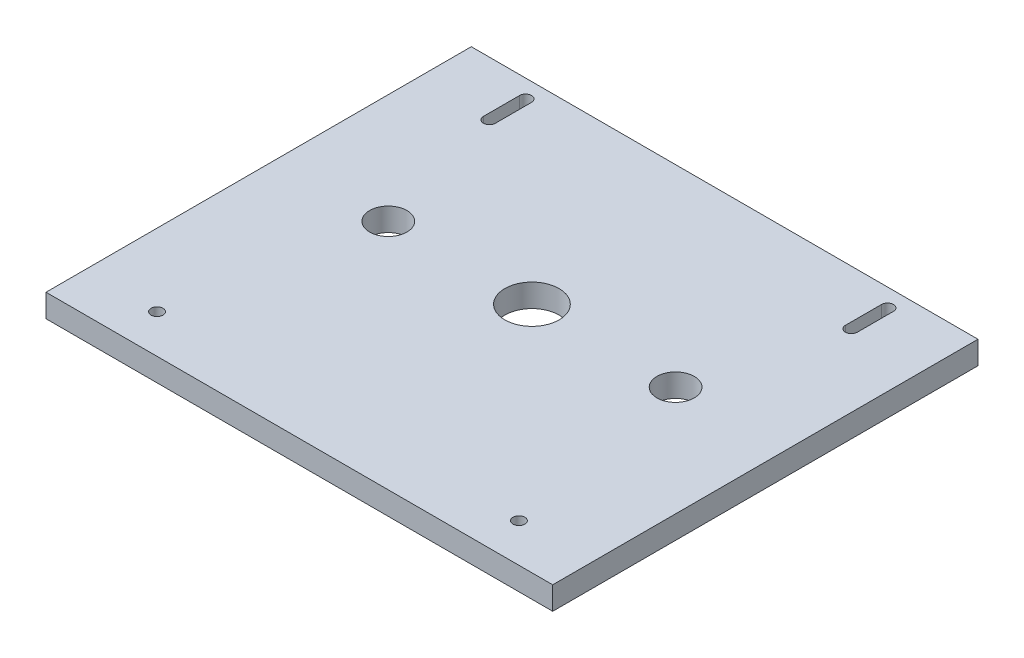
SolidWorks part; units mm, degrees
ref_plane "Front Plane" through (0, 0, 0) normal (0, 0, 1) x (1, 0, 0)
ref_plane "Top Plane" through (0, 0, 0) normal (0, 1, 0) x (1, 0, 0)
ref_plane "Right Plane" through (0, 0, 0) normal (1, 0, 0) x (0, 0, -1)
sketch "Sketch1" plane through (0, 0, 0) normal (0, 1, 0) x (1, 0, 0)
  line L1 (0, 0) -> (140, 0)
  line L2 (0, 0) -> (0, 117.505)
  line L3 (0, 117.505) -> (140, 117.505)
  line L4 (140, 0) -> (140, 117.505)
  dimension "D1" = 117.505
  dimension "D2" = 140
extrude "Boss-Extrude1" add sketch "Sketch1" along normal blind 6.35
sketch "Sketch2" plane through (0, 6.35, 0) normal (0, 1, 0) x (1, 0, 0)
  line L1 (0, 117.505) -> (0, 0) construction
  line L2 (140, 0) -> (140, 117.505) construction
  line L3 (70, 117.505) -> (70, 0) construction
  line L4 (140, 117.505) -> (0, 117.505) construction
  line L5 (0, 0) -> (140, 0) construction
  line L6 (0, 10.675) -> (140, 10.675) construction
  line L7 (0, 107.505) -> (140, 107.505) construction
  line L8 (120, 102.505) -> (120, 112.505) construction
  line L11 (20, 102.505) -> (20, 112.505) construction
  line L12 (18.35, 102.505) -> (18.35, 112.505)
  line L13 (21.65, 102.505) -> (21.65, 112.505)
  line L14 (121.65, 102.505) -> (121.65, 112.505)
  line L17 (118.35, 102.505) -> (118.35, 112.505)
  circle A0 centre (20, 10.675) radius 1.65
  arc A6 (18.35, 102.505) -> (21.65, 102.505) centre (20, 102.505) ccw
  arc A7 (21.65, 112.505) -> (18.35, 112.505) centre (20, 112.505) ccw
  circle A12 centre (70, 64.265) radius 7.5
  circle A15 centre (30.3125, 64.265) radius 5.16
  circle A16 centre (120, 10.675) radius 1.65
  circle A17 centre (109.6875, 64.265) radius 5.16
  arc A18 (121.65, 102.505) -> (118.35, 102.505) centre (120, 102.505) cw
  arc A19 (118.35, 112.505) -> (121.65, 112.505) centre (120, 112.505) cw
  point P26 (120, 107.505)
  point P33 (20, 107.505)
  dimension "D5" = 3.3
  dimension "D10" = 15
  dimension "D8" = 10.32
  dimension "D2" = 5
  dimension "D3" = 50
  dimension "D4" = 50
  dimension "D6" = 3.3
  dimension "D7" = 10
  dimension "D9" = 39.6875
  dimension "D11" = 10.675
  dimension "D13" = 53.59
extrude "Cut-Extrude1" cut sketch "Sketch2" against normal through all
